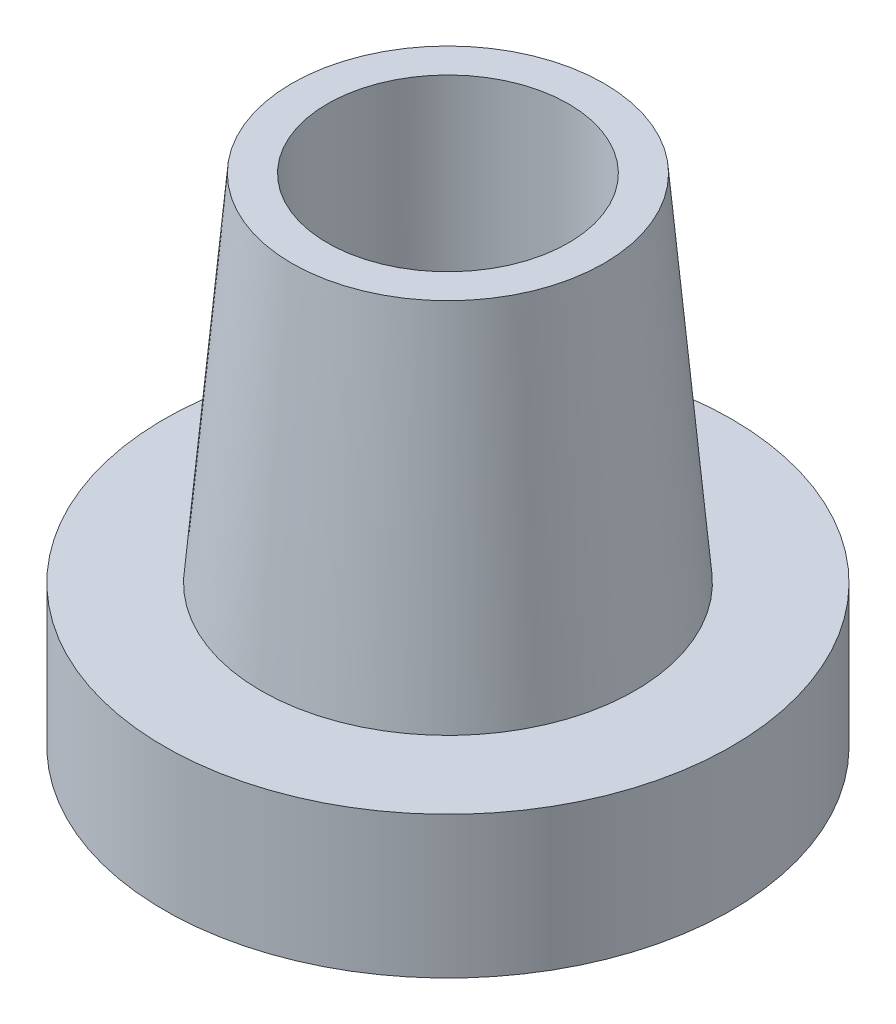
SolidWorks part; units mm, degrees
ref_plane "Front Plane" through (0, 0, 0) normal (0, 0, 1) x (1, 0, 0)
ref_plane "Top Plane" through (0, 0, 0) normal (0, 1, 0) x (1, 0, 0)
ref_plane "Right Plane" through (0, 0, 0) normal (1, 0, 0) x (0, 0, -1)
sketch "Sketch1" plane through (0, 0, 0) normal (0, 0, 1) x (1, 0, 0)
  line L1 (-40, 0) -> (-40, 20)
  line L2 (-40, 20) -> (-26.3744, 20)
  line L3 (-26.3744, 20) -> (-22, 70)
  line L4 (-22, 70) -> (-17, 70)
  line L5 (-17, 70) -> (-17, 0)
  line L7 (-40, 0) -> (-17, 0)
  line L8 (0, 0) -> (0, 50) construction
  dimension "D1" = 17
  dimension "D2" = 95
  dimension "D3" = 5
  dimension "D4" = 20
  dimension "D5" = 23
  dimension "D6" = 70
revolve "Revolve1" add sketch "Sketch1" angle 360 about L8
sketch "Sketch2" plane through (0, 0, 0) normal (0, -1, 0) x (1, 0, 0)
  circle A0 centre (0, 0) radius 19
thread "Thread2" pitch 2 method cut profile "Thread Profile2" start angle 0, offset 0, length 15, pitch 3, diameter 34
ref_plane "Plane2" through (17, 0, 0) normal (0, 0, 1) x (1, 0, 0)
sketch "Thread Profile2" plane through (17, 0, 0) normal (0, 0, 1) x (1, 0, 0)
  line L0 (0, 0) -> (0, 2) construction
  line L1 (0, 0) -> (1.0825, 0.625)
  line L2 (1.0825, 0.625) -> (1.0825, 0.875)
  line L3 (1.0825, 0.875) -> (0, 1.5)
  line L4 (1.0825, 0.75) -> (0, 0.75) construction
  line L11 (0, 0) -> (0, 1.5)
  point P2 (0, 0)
  dimension "Pitch" = 2
  dimension "Profile_Angle" = 60
  dimension "Profile_Land" = 0.25
  dimension "Profile_Height" = 1.0825
